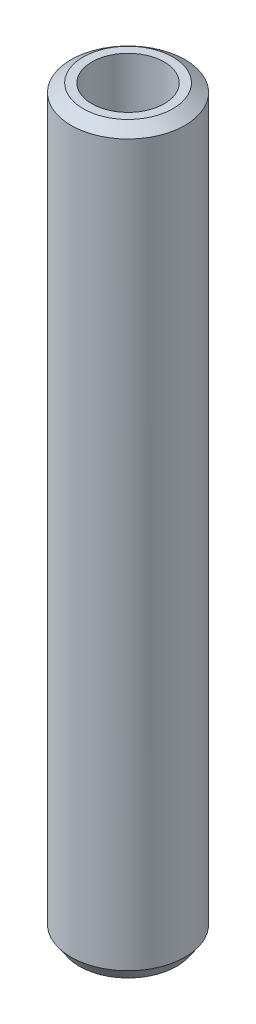
SolidWorks part; units mm, degrees
ref_plane "Front Plane" through (0, 0, 0) normal (0, 0, 1) x (1, 0, 0)
ref_plane "Top Plane" through (0, 0, 0) normal (0, 1, 0) x (1, 0, 0)
ref_plane "Right Plane" through (0, 0, 0) normal (1, 0, 0) x (0, 0, -1)
sketch "Sketch1" plane through (0, 0, 0) normal (0, 1, 0) x (1, 0, 0)
  circle A0 centre (0, 0) radius 12.5
  dimension "SHAFT_OD" = 25
extrude "Boss-Extrude1" add sketch "Sketch1" along normal blind 162.456
sketch "Sketch2" plane through (0, 0, 0) normal (0, 1, 0) x (1, 0, 0)
  circle A0 centre (0, 0) radius 7.9429
  dimension "BORE_D" = 15.8858
extrude "Cut-Extrude1" cut sketch "Sketch2" along normal through all
chamfer "Chamfer1" distance 1.8319 angle 55.506 2 edges at (0, 162.456, 12.5) (0, 0, 12.5) first distance on face at (0, 162.456, 12.5) first distance on face at (0, 0, 7.9429)
